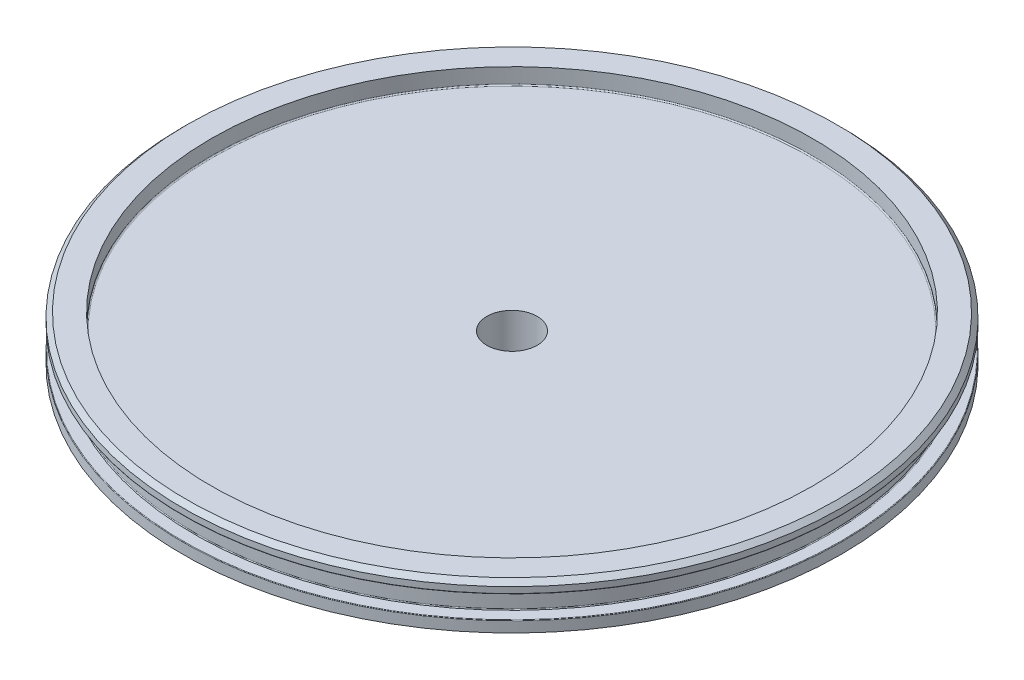
SolidWorks part; units mm, degrees
material "6061-T6 (SS)"
ref_plane "Front Plane" through (0, 0, 0) normal (0, 0, 1) x (1, 0, 0)
ref_plane "Top Plane" through (0, 0, 0) normal (0, 1, 0) x (1, 0, 0)
ref_plane "Right Plane" through (0, 0, 0) normal (1, 0, 0) x (0, 0, -1)
sketch "Sketch1" plane through (0, 0, 0) normal (0, 0, 1) x (1, 0, 0)
  line L0 (0, 48.1922) -> (0, -25.6743) construction
  line L1 (0, 0) -> (72.898, 0)
  line L2 (72.898, 0) -> (72.898, 2.4638)
  line L3 (72.898, 2.4638) -> (70.0532, 2.4638)
  line L4 (70.0532, 2.4638) -> (70.0532, 7.4422)
  line L5 (70.0532, 7.4422) -> (72.898, 7.4422)
  line L6 (72.898, 7.4422) -> (72.898, 9.906)
  line L7 (72.898, 9.906) -> (66.548, 9.906)
  line L8 (66.548, 9.906) -> (66.548, 6.35)
  line L9 (66.548, 6.35) -> (0, 6.35)
  line L10 (0, 6.35) -> (0, 0)
  dimension "D1" = 145.796
  dimension "D2" = 4.9784
  dimension "D3" = 2.8448
  dimension "D4" = 9.906
  dimension "D5" = 6.35
  dimension "D6" = 6.35
revolve "Revolve1" add sketch "Sketch1" angle 360 about L0
sketch "Sketch6" plane through (0, 0, 0) normal (0, -1, 0) x (1, 0, 0)
  circle A0 centre (0, 0) radius 66.04
  dimension "D1" = 132.08
extrude "Boss-Extrude1" add sketch "Sketch6" along normal blind 2.54
hole_wizard "Pipe Tap Drill for 1/4 Tap - GN2" positions "Sketch2" profile "Sketch3" hole size "1/4" standard "ANSI Inch" end condition through all
sketch "Sketch2" plane through (0, 6.35, 0) normal (0, 1, 0) x (1, 0, 0)
  point P4 (0, 0)
  dimension "D1" = 0
sketch "Sketch3" plane through (0, 6.35, 0) normal (1, 0, 0) x (0, 0, 1)
  line L0 (0, 0) -> (0, 8.89)
  line L1 (0, 8.89) -> (5.5626, 8.89)
  line L2 (5.5626, 8.89) -> (5.5626, 0)
  line L5 (5.5626, 0) -> (0, 0)
  line L11 (0, -6.35) -> (0, 107.95) construction
  dimension "Thru Hole Dia." = 11.1252
  dimension "Thru Hole Depth" = 8.89
fillet "CNC ID Fillet" radius 0.1778 3 edges at (-70.0532, 7.4422, 0) (-70.0532, 2.4638, 0) (66.04, 0, 0)
fillet "CNC OD Fillet" radius 0.127 3 edges at (-72.898, 7.4422, 0) (-72.898, 2.4638, 0) (66.04, -2.54, 0)
chamfer "CNC Chamfers" distance 1.016 angle 45 1 edges at (-72.898, 9.906, 0)
fillet "CNC Bore Fillet" radius 0.254 1 edges at (-66.548, 6.35, 0)
